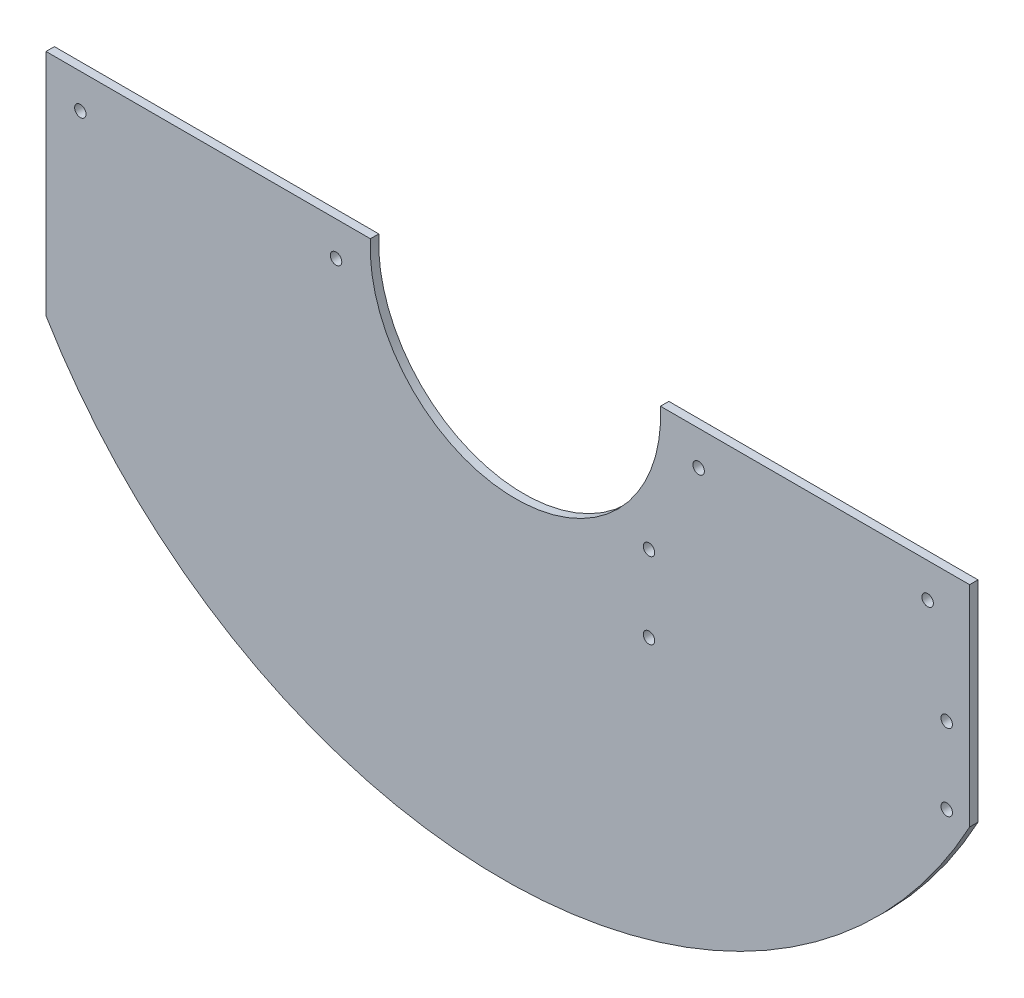
SolidWorks part; units mm, degrees
ref_plane "Front Plane" through (0, 0, 0) normal (0, 0, 1) x (1, 0, 0)
ref_plane "Top Plane" through (0, 0, 0) normal (0, 1, 0) x (1, 0, 0)
ref_plane "Right Plane" through (0, 0, 0) normal (1, 0, 0) x (0, 0, -1)
sketch "Sketch2" plane through (0, 0, 0) normal (0, 0, 1) x (1, 0, 0)
  line L0 (-751.1308, 0) -> (36805.4106, 0) construction
  line L1 (-121.5, 0) -> (-36.5, 0)
  line L2 (-751.1308, -128) -> (36805.4106, -128) construction
  line L3 (120.5, 0) -> (39.5, 0)
  line L4 (-981.5234, -40) -> (49018.4766, -40) construction
  line L5 (-121.5, -1011.0347) -> (-121.5, 48988.9653) construction
  line L6 (120.5, -1006.9287) -> (120.5, 48993.0713) construction
  line L7 (-121.5, 0) -> (-121.5, -60)
  line L8 (120.5, 0) -> (120.5, -55)
  arc A2 (-36.5, 0) -> (39.5, 0) centre (1.5, -1.95) ccw
  arc A3 (-121.5, -60) -> (120.5, -55) centre (-1.9183, 11.1455) ccw
  dimension "D1" = 128
  dimension "D2" = 40
  dimension "D3" = 121.5
  dimension "D4" = 120.5
  dimension "D5" = 81
  dimension "D6" = 60
  dimension "D7" = 85
  dimension "D8" = 55
extrude "Boss-Extrude1" add sketch "Sketch2" along normal blind 2.2
ref_plane "Plane3" through (0, -9, 0) normal (0, 1, 0) x (1, 0, 0)
ref_axis "Axis1" through (120.5, -9, 2.2) along (-1, 0, 0)
sketch "Sketch4" plane through (0, 0, 2.2) normal (0, 0, 1) x (1, 0, 0)
  line L0 (1.21, -9) -> (-1.21, -9) construction
  line L1 (120.5, -55) -> (120.5, 0) construction
  line L2 (-121.5, 0) -> (-121.5, -60) construction
  circle A0 centre (109.5, -9) radius 1.5
  circle A1 centre (49.5, -9) radius 1.5
  circle A2 centre (-45.5, -9) radius 1.5
  circle A3 centre (-112.5, -9) radius 1.5
  dimension "D1" = 11
  dimension "D2" = 60
  dimension "D3" = 9
  dimension "D4" = 67
extrude "Cut-Extrude1" cut sketch "Sketch4" against normal up to next
ref_plane "Plane4" through (114.5, 0, 0) normal (1, 0, 0) x (0, 0, -1)
ref_axis "Axis2" through (114.5, -55.124, 2.2) along (0, 1, 0)
sketch "Sketch5" plane through (0, 0, 2.2) normal (0, 0, 1) x (1, 0, 0)
  line L0 (114.5, -1.21) -> (114.5, 1.21) construction
  line L1 (55, 0) -> (-55, 0) construction
  circle A0 centre (114.5, -34) radius 1.5
  circle A1 centre (114.5, -54) radius 1.5
  circle A2 centre (36.5, -34) radius 1.5
  circle A3 centre (36.5, -54) radius 1.5
  dimension "D1" = 3
  dimension "D2" = 3
  dimension "D5" = 3
  dimension "D6" = 3
  dimension "D3" = 34
  dimension "D4" = 20
  dimension "D7" = 78
extrude "Cut-Extrude2" cut sketch "Sketch5" against normal up to next
